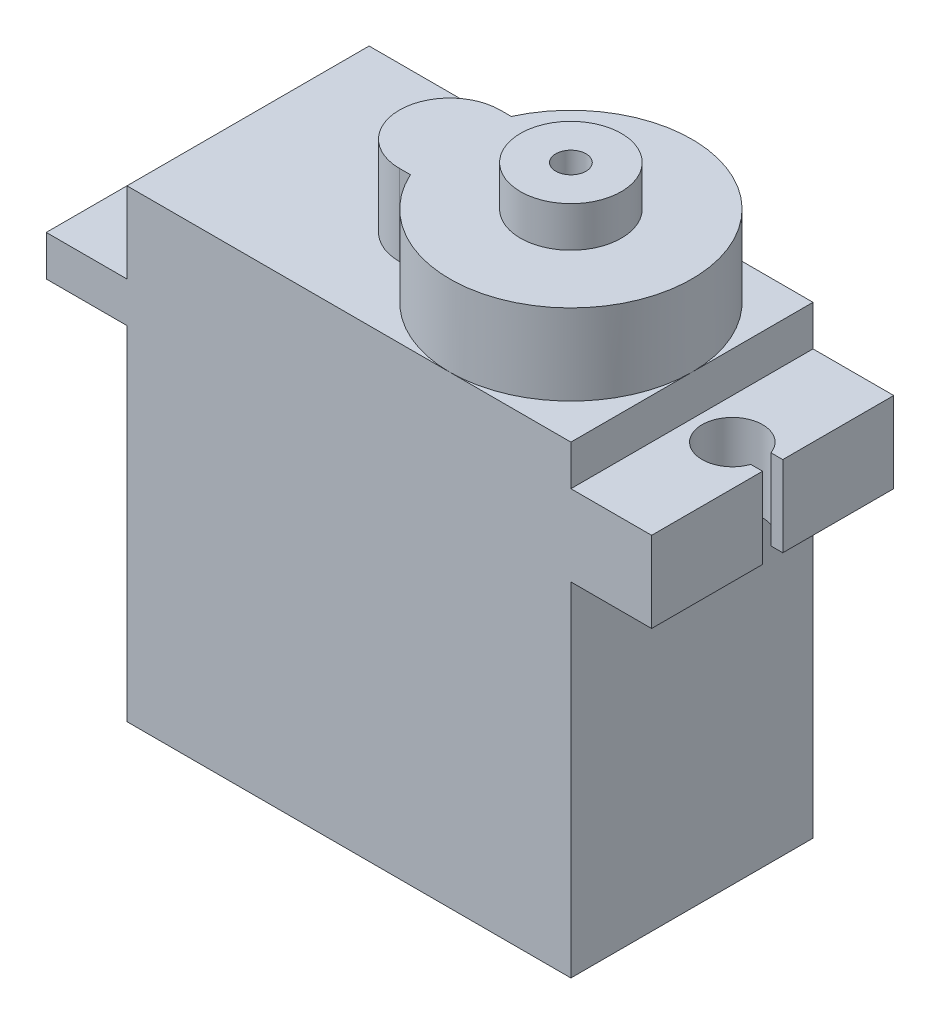
SolidWorks part; units mm, degrees
ref_plane "Alzado" through (0, 0, 0) normal (0, 0, 1) x (1, 0, 0)
ref_plane "Planta" through (0, 0, 0) normal (0, 1, 0) x (1, 0, 0)
ref_plane "Vista lateral" through (0, 0, 0) normal (1, 0, 0) x (0, 0, -1)
sketch "Croquis1" plane through (0, 0, 0) normal (0, 0, 1) x (1, 0, 0)
  line L0 (-36.1403, 11.0751) -> (-14.1403, 11.0751)
  line L1 (-14.1403, 11.0751) -> (-14.1403, -11.9249)
  line L2 (-14.1403, -11.9249) -> (-36.1403, -11.9249)
  line L3 (-36.1403, -11.9249) -> (-36.1403, 11.0751)
extrude "Saliente-Extruir1" add sketch "Croquis1" along normal blind 12
sketch "Croquis2" plane through (-14.1403, 0, 0) normal (1, 0, 0) x (0, 0, -1)
  line L0 (-12, 11.0751) -> (-12, 7.0751) construction
  line L1 (-12, -11.9249) -> (-12, 11.0751) construction
  line L2 (-12, 7.0751) -> (0, 7.0751)
  line L3 (0, -11.9249) -> (0, 11.0751) construction
  line L4 (0, 7.0751) -> (0, 5.0751)
  line L5 (0, 5.0751) -> (-12, 5.0751)
  line L6 (-12, 5.0751) -> (-12, 7.0751)
extrude "Saliente-Extruir2" add sketch "Croquis2" along normal blind 5
sketch "Croquis3" plane through (0, 7.0751, 0) normal (0, 1, 0) x (1, 0, 0)
  line L0 (-9.1403, -12) -> (-9.1403, 0) construction
  line L1 (-9.1403, 0) -> (-9.1403, -6) construction
  line L2 (-10.1403, -6) -> (-12.1403, -6) construction
  line L3 (-12.1403, -6) -> (-12.1403, -4.5) construction
  line L4 (-12.1403, -4.5) -> (-10.6403, -4.5) construction
  line L5 (-10.6403, -4.5) -> (-10.6403, -7.5) construction
  line L6 (-10.6403, -7.5) -> (-13.6403, -7.5) construction
  line L7 (-13.6403, -7.5) -> (-13.6403, -4.5) construction
  line L8 (-13.6403, -4.5) -> (-12.1403, -4.5) construction
  line L9 (-10.1403, -6) -> (-10.1403, -5.5) construction
  line L10 (-10.1403, -6) -> (-10.1403, -6.5) construction
  line L11 (-10.1403, -5.5) -> (-10.7261, -5.5)
  line L12 (-10.7261, -6.5) -> (-10.1403, -6.5)
  line L14 (-9.1403, -2.0976) -> (-10.1403, -2.0976) construction
  line L15 (-10.1403, -5.5) -> (-10.1403, 0)
  line L16 (-9.1403, 0) -> (-14.1403, 0) construction
  line L17 (-10.1403, 0) -> (-9.1403, 0)
  line L18 (-9.1403, 0) -> (-9.1403, -12)
  line L19 (-9.1403, -12) -> (-10.1403, -12)
  line L20 (-9.1403, -12) -> (-14.1403, -12) construction
  line L21 (-10.1403, -12) -> (-10.1403, -6.5)
  arc A0 (-10.7261, -6.5) -> (-10.7261, -5.5) centre (-12.1403, -6) cw
extrude "Cortar-Extruir2" cut sketch "Croquis3" against normal blind 2
mirror "Simetría1" about plane through (-9.1403, 7.0751, 12) normal (0, -1, 0) of "Saliente-Extruir2", "Cortar-Extruir2"
sketch "Croquis13" plane through (-36.1403, 0, 0) normal (-1, 0, 0) x (0, 0, 1)
  line L0 (0, 11.0751) -> (0, 7.0751) construction
  line L1 (0, 11.0751) -> (0, -11.9249) construction
  line L2 (0, 7.0751) -> (12, 7.0751)
  line L3 (12, 11.0751) -> (12, -11.9249) construction
  line L4 (12, 7.0751) -> (12, 5.0751)
  line L5 (12, 5.0751) -> (0, 5.0751)
  line L6 (0, 5.0751) -> (0, 7.0751)
extrude "Saliente-Extruir3" add sketch "Croquis13" along normal blind 4
sketch "Croquis14" plane through (0, 7.0751, 0) normal (0, 1, 0) x (1, 0, 0)
  line L0 (-40.1403, -6) -> (-40.1403, -5.5) construction
  line L1 (-40.1403, 0) -> (-40.1403, -12) construction
  line L2 (-40.1403, -12) -> (-40.1403, -6) construction
  line L3 (-40.1403, -6.5) -> (-40.1403, -5.5)
  line L4 (-36.6403, -6) -> (-36.6403, -4.5) construction
  line L5 (-36.6403, -4.5) -> (-39.6403, -4.5) construction
  line L6 (-39.6403, -4.5) -> (-39.6403, -7.5) construction
  line L7 (-39.6403, -7.5) -> (-36.6403, -7.5) construction
  line L8 (-36.6403, -7.5) -> (-36.6403, -6) construction
  line L9 (-40.1403, -6) -> (-40.1403, -6.5) construction
  line L10 (-40.1403, -6.5) -> (-39.5545, -6.5)
  line L11 (-40.1403, -5.5) -> (-39.5545, -5.5)
  line L12 (-39.6403, -6) -> (-36.6403, -6) construction
  arc A0 (-39.5545, -5.5) -> (-39.5545, -6.5) centre (-38.1403, -6) cw
extrude "Cortar-Extruir3" cut sketch "Croquis14" against normal blind 2
sketch "Croquis15" plane through (0, 11.0751, 0) normal (0, 1, 0) x (1, 0, 0)
  line L0 (-14.1403, 0) -> (-14.1403, -12) construction
  line L1 (-14.1403, -12) -> (-14.1403, -6) construction
  line L2 (-14.1403, -6) -> (-20.1403, -6) construction
  line L3 (-20.1403, -6) -> (-20.1403, 0) construction
  line L4 (-14.1403, 0) -> (-36.1403, 0) construction
  line L5 (-20.1403, 0) -> (-20.1403, -12) construction
  line L6 (-14.1403, -12) -> (-36.1403, -12) construction
  line L7 (-20.1403, -6) -> (-26.1403, -6) construction
  line L8 (-26.1403, -6) -> (-26.1403, 0) construction
  line L9 (-26.1403, 0) -> (-26.1403, -12) construction
  line L10 (-26.1403, -6) -> (-26.1403, -3.5) construction
  line L11 (-26.1403, -3.5) -> (-28.6403, -3.5) construction
  line L12 (-28.6403, -3.5) -> (-28.6403, -8.5) construction
  line L13 (-28.6403, -8.5) -> (-26.1403, -8.5) construction
  line L14 (-26.1403, -8.5) -> (-25.5947, -8.5)
  line L15 (-26.1403, -3.5) -> (-25.5947, -3.5)
  arc A0 (-26.1403, -8.5) -> (-26.1403, -3.5) centre (-26.1403, -6) cw
  arc A1 (-25.5947, -3.5) -> (-25.5947, -8.5) centre (-20.1403, -6) cw
extrude "Saliente-Extruir4" add sketch "Croquis15" along normal blind 4 contours A1 L15 A0 L14 region at (-20.7423, 11.0751, 6)
sketch "Croquis16" plane through (0, 11.0751, 0) normal (0, 1, 0) x (1, 0, 0)
  line L0 (-14.1403, -6) -> (-20.1403, -6) construction
  line L1 (-14.1403, -12) -> (-14.1403, 0) construction
  circle A0 centre (-20.1403, -6) radius 2.5
extrude "Saliente-Extruir5" add sketch "Croquis16" along normal blind 6
sketch "Croquis21" plane through (0, 17.0751, 0) normal (0, 1, 0) x (1, 0, 0)
  circle A0 centre (-20.1403, -6) radius 0.75
extrude "Cortar-Extruir6" cut sketch "Croquis21" against normal blind 2
